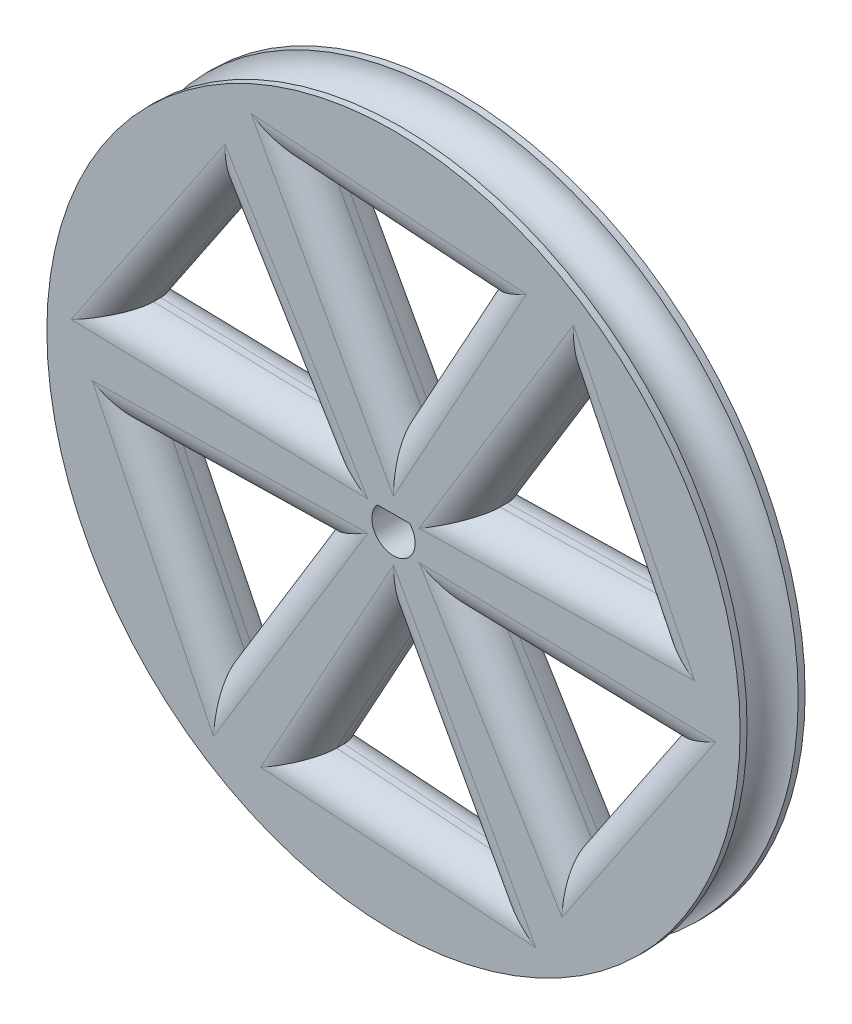
SolidWorks part; units mm, degrees
ref_plane "Front Plane" through (0, 0, 0) normal (0, 0, 1) x (1, 0, 0)
ref_plane "Top Plane" through (0, 0, 0) normal (0, 1, 0) x (1, 0, 0)
ref_plane "Right Plane" through (0, 0, 0) normal (1, 0, 0) x (0, 0, -1)
sketch "Sketch4" plane through (0, 0, 0) normal (1, 0, 0) x (0, 0, -1)
  line L0 (4.02, 24) -> (4.5, 24)
  line L1 (0, 0) -> (4.5, 0)
  line L2 (0, 0) -> (0, 24)
  line L3 (0, 24) -> (0.48, 24)
  line L4 (4.5, 0) -> (4.5, 24)
  arc A0 (0.48, 24) -> (4.02, 24) centre (2.25, 24) ccw
  dimension "D3" = 3.54
  dimension "D1" = 4.5
  dimension "D2" = 24
revolve "Revolve1" add sketch "Sketch4" angle 360 about L1
sketch "Sketch5" plane through (0, 0, 0) normal (0, 0, 1) x (1, 0, 0)
  line L3 (-1.118, 1) -> (1.118, 1)
  arc A0 (-1.118, 1) -> (1.118, 1) centre (0, 0) ccw
  dimension "D1" = 3
extrude "Cut-Extrude2" cut sketch "Sketch5" against normal blind 5
sketch "Sketch6" plane through (0, 0, 0) normal (0, 0, 1) x (1, 0, 0)
  line L0 (0, 6.2104) -> (-6.35, 17.8373)
  line L1 (-6.35, 17.8373) -> (5.9324, 16.9978)
  line L2 (5.9324, 16.9978) -> (0, 6.2104)
extrude "Cut-Extrude3" cut sketch "Sketch6" against normal blind 5
pattern_circular "CirPattern2" count 6 every 60 about axis through (0, 0, 0) along (0, 0, 1) of "Cut-Extrude3"
fillet "Fillet10" radius 2 1 edges at (-3.175, 12.0238, 0)
fillet "Fillet11" radius 2 1 edges at (-8.5663, 8.3709, 0)
fillet "Fillet12" radius 2 1 edges at (-14.5734, 9.4429, 0)
fillet "Fillet13" radius 2 1 edges at (-12.0004, 3.2623, 0)
fillet "Fillet14" radius 2 1 edges at (2.3945, 10.5646, 0)
fillet "Fillet15" radius 2 1 edges at (8.8255, 8.7615, 0)
fillet "Fillet16" radius 2 1 edges at (10.3464, 3.2085, 0)
fillet "Fillet17" radius 2 1 edges at (-0.2925, 17.4233, 0)
fillet "Fillet18" radius 2 1 edges at (14.9428, 8.9649, 0)
fillet "Fillet19" radius 2 1 edges at (12.0004, -3.2623, 0)
fillet "Fillet20" radius 2 1 edges at (7.9519, -7.356, 0)
fillet "Fillet21" radius 2 8 edges at (-14.9797, -8.8896, -4.5) (-14.9797, -8.8896, 0) (-11.5325, -3.2332, 0) (-8.8255, -8.7615, -4.5) (-2.9662, -11.6041, 0) (0.2088, -17.4175, 0) (3.175, -12.0238, -4.5) (15.2352, -8.4584, 0)
fillet "Fillet22" radius 2 1 edges at (3.175, -12.0238, 0)
fillet "Fillet23" radius 2 1 edges at (-8.8255, -8.7615, 0)
fillet "Fillet24" radius 2 15 edges at (1.3924, -17.4984, -4.5) (-2.3945, -10.5646, -4.5) (-11.4487, -3.2315, -4.5) (-12.0004, 3.2623, -4.5) (-15.1884, 8.528, -4.5) (-8.5663, 8.3709, -4.5) (-3.175, 12.0238, -4.5) (-0.2088, 17.4175, -4.5) (2.9662, 11.6041, -4.5) (8.8255, 8.7615, -4.5) (14.9797, 8.8896, -4.5) (11.5325, 3.2332, -4.5) (8.5663, -8.3709, -4.5) (12.0004, -3.2623, -4.5) (15.1884, -8.528, -4.5)
